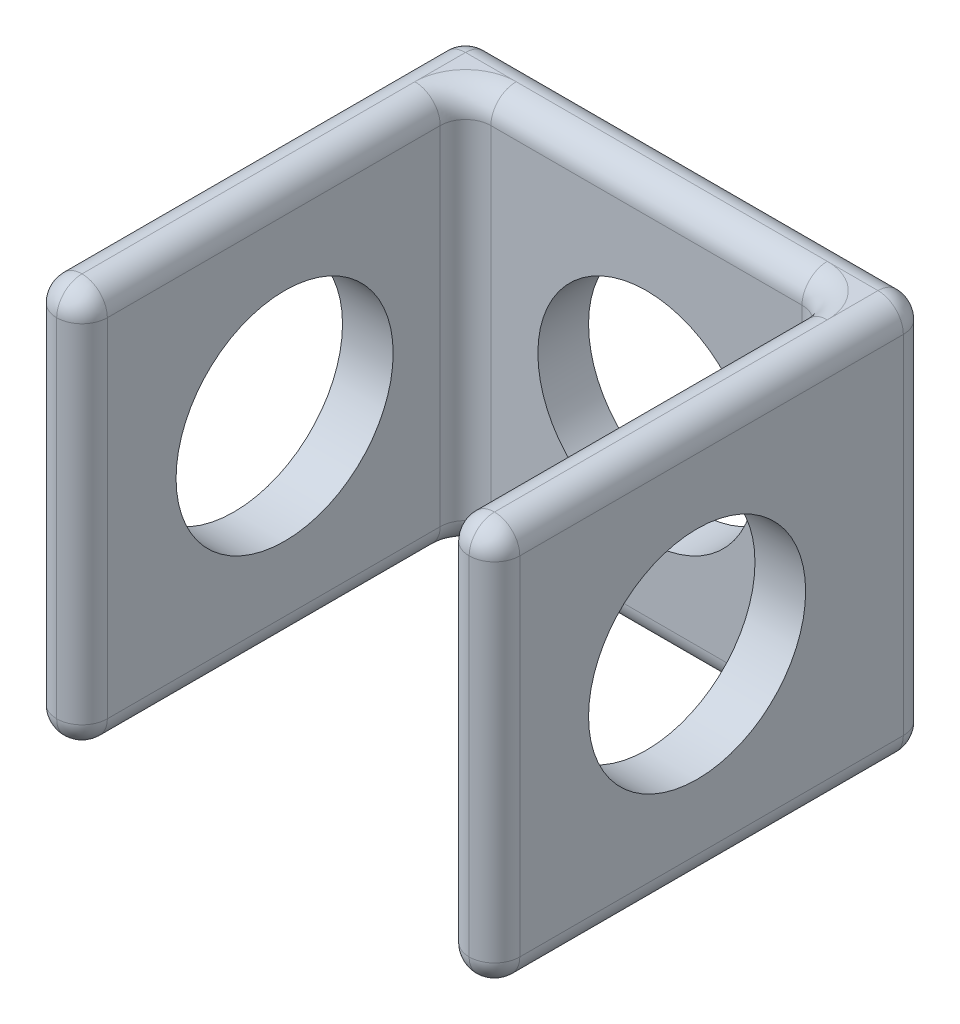
SolidWorks part; units mm, degrees
ref_plane "Front Plane" through (0, 0, 0) normal (0, 0, 1) x (1, 0, 0)
ref_plane "Top Plane" through (0, 0, 0) normal (0, 1, 0) x (1, 0, 0)
ref_plane "Right Plane" through (0, 0, 0) normal (1, 0, 0) x (0, 0, -1)
sketch "Sketch1" plane through (0, 0, 0) normal (0, 1, 0) x (1, 0, 0)
  line L1 (0, 0) -> (128, 0)
  line L2 (0, 0) -> (0, 120)
  line L3 (0, 120) -> (128, 120)
  line L4 (128, 0) -> (128, 120)
  dimension "D1" = 120
  dimension "D2" = 128
extrude "Boss-Extrude1" add sketch "Sketch1" along normal blind 110
sketch "Sketch2" plane through (0, 110, 0) normal (0, 1, 0) x (1, 0, 0)
  line L0 (14, 0) -> (14, 120) construction
  line L1 (0, 0) -> (128, 0) construction
  line L2 (128, 120) -> (0, 120) construction
  line L3 (0, 120) -> (0, 0) construction
  line L4 (114, 120) -> (114, 0) construction
  line L5 (128, 0) -> (128, 120) construction
  line L6 (14, 106) -> (114, 106) construction
  line L7 (14, 0) -> (14, 106)
  line L8 (14, 106) -> (114, 106)
  line L9 (114, 106) -> (114, 0)
  line L10 (14, 0) -> (114, 0)
  dimension "D1" = 14
  dimension "D2" = 14
  dimension "D3" = 14
extrude "Cut-Extrude2" cut sketch "Sketch2" against normal through all
sketch "Sketch3" plane through (0, 0, 0) normal (-1, 0, 0) x (0, 0, 1)
  line L0 (-120, 55) -> (0, 55) construction
  line L1 (-120, 110) -> (-120, 0) construction
  line L2 (0, 110) -> (0, 0) construction
  line L3 (-86, 45.8781) -> (-86, 88.0416) construction
  circle A0 centre (-56, 55) radius 30
  point P9 (0, 0)
  dimension "D1" = 60
  dimension "D2" = 34
extrude "Cut-Extrude3" cut sketch "Sketch3" against normal through all
sketch "Sketch4" plane through (0, 0, -106) normal (0, 0, 1) x (1, 0, 0)
  line L0 (14, 110) -> (114, 0) construction
  circle A0 centre (64, 55) radius 30
  dimension "D1" = 60
extrude "Cut-Extrude4" cut sketch "Sketch4" against normal through all
fillet "Fillet1" radius 7 24 edges at (128, 55, 0) (121, 0, 0) (114, 55, 0) (121, 110, 0) (0, 55, 0) (7, 110, 0) (14, 55, 0) (7, 0, 0) (64, 0, -106) (114, 0, -53) (128, 0, -60) (64, 0, -120) (0, 0, -60) (14, 0, -53) (0, 110, -60) (64, 110, -120) (128, 110, -60) (114, 110, -53) (64, 110, -106) (14, 110, -53) (128, 55, -120) (0, 55, -120) (114, 55, -106) (14, 55, -106)
